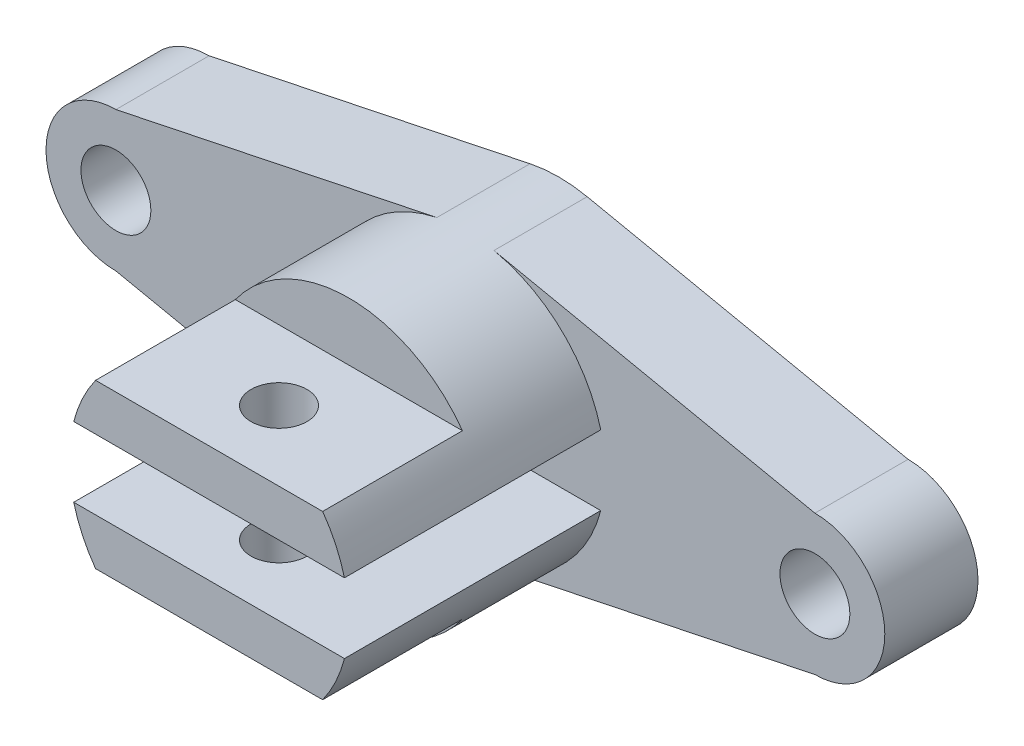
SolidWorks part; units mm, degrees
ref_plane "Alzado" through (0, 0, 0) normal (0, 0, 1) x (1, 0, 0)
ref_plane "Planta" through (0, 0, 0) normal (0, 1, 0) x (1, 0, 0)
ref_plane "Vista lateral" through (0, 0, 0) normal (1, 0, 0) x (0, 0, -1)
sketch "Croquis1" plane through (0, 0, 0) normal (0, 0, 1) x (1, 0, 0)
  line L4 (-29.0474, 7.5) -> (29.0474, 7.5)
  line L5 (-29.0474, -7.5) -> (29.0474, -7.5)
  line L6 (-30, 0) -> (30, 0) construction
  line L7 (24.367, 17.5) -> (-24.367, 17.5)
  line L8 (-24.367, -17.5) -> (24.367, -17.5)
  line L9 (-75, 15) -> (-6.1264, 29.3678)
  line L10 (-75, -15) -> (-6.1264, -29.3678)
  line L11 (75, 15) -> (6.1264, 29.3678)
  line L12 (75, -15) -> (6.1264, -29.3678)
  arc A0 (-29.0474, -7.5) -> (29.0474, -7.5) centre (0, 0) ccw
  circle A1 centre (-75, 0) radius 7.5
  circle A2 centre (75, 0) radius 7.5
  arc A3 (-75, 15) -> (-75, -15) centre (-75, 0) ccw
  arc A4 (75, -15) -> (75, 15) centre (75, 0) ccw
  arc A5 (29.0474, 7.5) -> (-29.0474, 7.5) centre (0, 0) ccw
  dimension "D1" = 60
  dimension "D3" = 15
  dimension "D5" = 30
  dimension "D6" = 7.5
  dimension "D2" = 75
  dimension "D4" = 75
  dimension "D7" = 7.5
  dimension "D8" = 60
  dimension "D9" = 17.5
  dimension "D10" = 17.5
extrude "Saliente-Extruir1" add sketch "Croquis1" along normal blind 20 contours A5 L4 A3 A0 L5 A4 A1 A2 region at (0, 0, 0)
extrude "Saliente-Extruir2" add sketch "Croquis1<3>" along normal blind 45 contours L7 A5 | L8 A0 region at (0, 22.6016, 0) region at (0, -22.6016, 0)
sketch "Croquis1<3>" plane through (0, 0, 0) normal (0, 0, 1) x (1, 0, 0) same geometry as "Croquis1"
extrude "Saliente-Extruir3" add sketch "Croquis1<4>" along normal blind 75 contours L4 A5 L7 | L5 A0 L8 region at (0, 12.3572, 0) region at (0, -12.3572, 0)
sketch "Croquis1<4>" plane through (0, 0, 0) normal (0, 0, 1) x (1, 0, 0) same geometry as "Croquis1"
sketch "Croquis2" plane through (0, -17.5, 0) normal (0, -1, 0) x (1, 0, 0)
  circle A0 centre (0, 60) radius 6
  dimension "D1" = 12
  dimension "D2" = 60
extrude "Cortar-Extruir1" cut sketch "Croquis2" against normal blind 75
